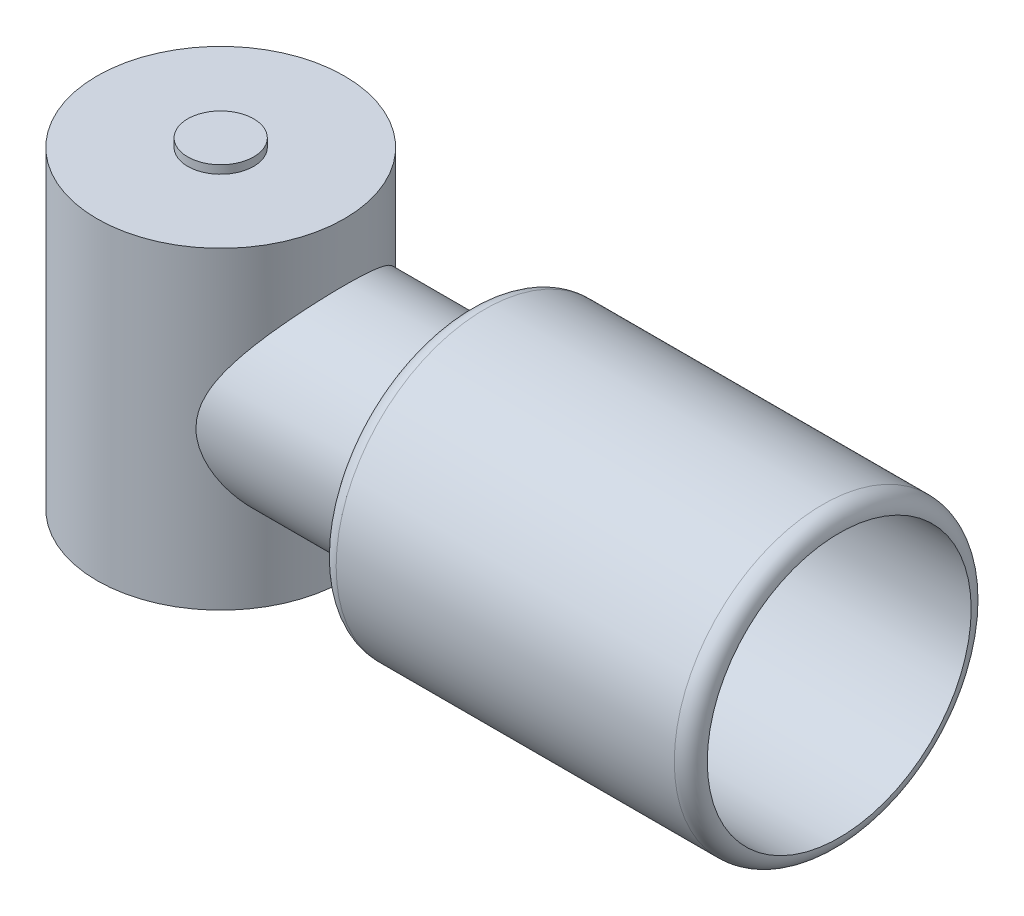
SolidWorks part; units mm, degrees
ref_plane "前视基准面" through (0, 0, 0) normal (0, 0, 1) x (1, 0, 0)
ref_plane "上视基准面" through (0, 0, 0) normal (0, 1, 0) x (1, 0, 0)
ref_plane "右视基准面" through (0, 0, 0) normal (1, 0, 0) x (0, 0, -1)
sketch "草图1" plane through (0, 0, 0) normal (0, 0, 1) x (1, 0, 0)
  line L0 (0, 20) -> (0, -23.9649) construction
  line L1 (0, 20) -> (-4, 20)
  line L2 (-4, 20) -> (-4, 19)
  line L3 (-4, 19) -> (-15, 19)
  line L4 (-15, 19) -> (-15, 0)
  line L5 (0, 0) -> (-15, 0)
  line L6 (0, 20) -> (0, 0)
  dimension "D1" = 20
  dimension "D2" = 19
  dimension "D3" = 30
  dimension "D4" = 8
revolve "旋转1" add sketch "草图1" angle 360 about L0
mirror "镜向1" about plane through (0, 0, 0) normal (0, -1, 0) of "旋转1"
sketch "草图2" plane through (0, 0, 0) normal (1, 0, 0) x (0, 0, -1)
  circle A0 centre (0, 0) radius 12
  dimension "D1" = 24
extrude "凸台-拉伸1" add sketch "草图2" along normal blind 30
sketch "草图3" plane through (30, 0, 0) normal (1, 0, 0) x (0, 0, -1)
  circle A0 centre (0, 0) radius 18
  dimension "D1" = 36
extrude "凸台-拉伸2" add sketch "草图3" along normal blind 45
sketch "草图4" plane through (75, 0, 0) normal (1, 0, 0) x (0, 0, -1)
  circle A0 centre (0, 0) radius 16
  circle A1 centre (0, 0) radius 18 construction
  dimension "D1" = 2
extrude "切除-拉伸1" cut sketch "草图4" against normal offset from surface (43 mm away) 2 up to face at (30, 0, -12)
fillet "圆角1" radius 2 2 edges at (75, 0, -18) (30, 0, -18)
